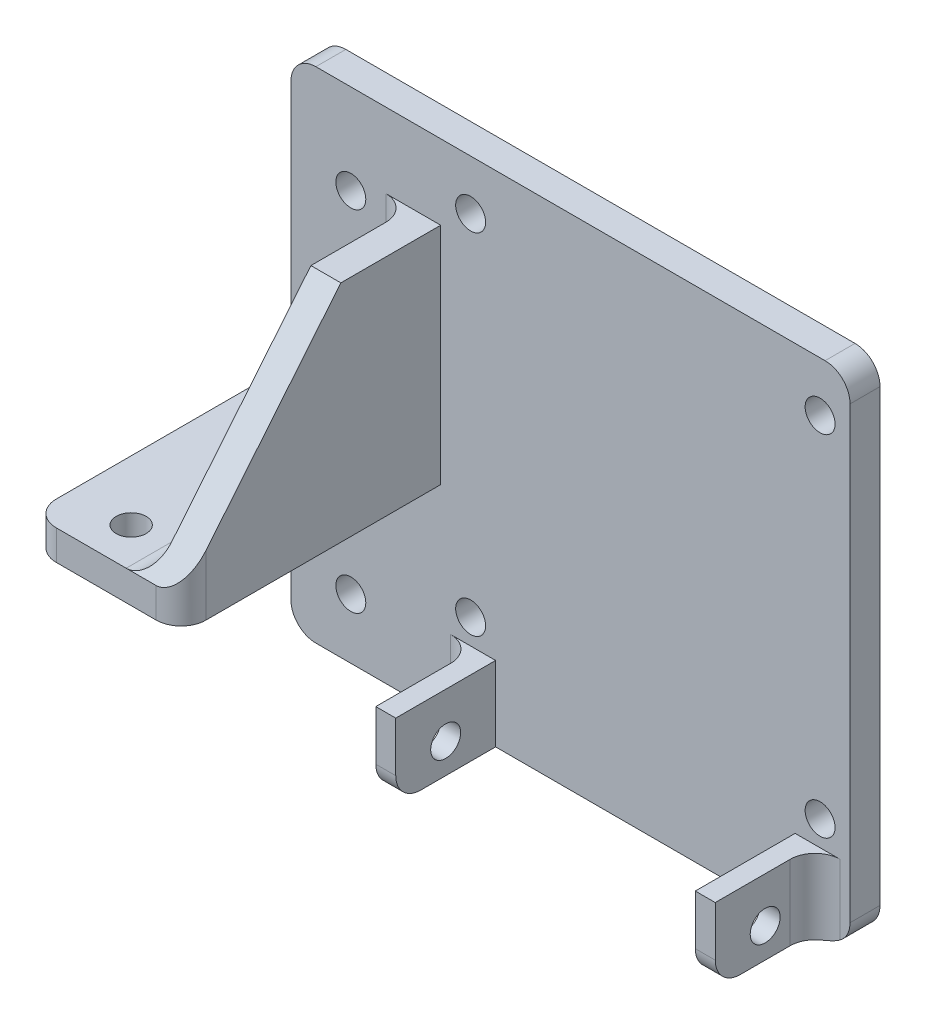
SolidWorks part; units mm, degrees
ref_plane "Front Plane" through (0, 0, 0) normal (0, 0, 1) x (1, 0, 0)
ref_plane "Top Plane" through (0, 0, 0) normal (0, 1, 0) x (1, 0, 0)
ref_plane "Right Plane" through (0, 0, 0) normal (1, 0, 0) x (0, 0, -1)
sketch "Sketch1" plane through (0, 0, 0) normal (0, 0, 1) x (1, 0, 0)
  line L1 (0, 0) -> (56, 0)
  line L2 (0, 0) -> (0, 50)
  line L3 (0, 50) -> (56, 50)
  line L4 (56, 0) -> (56, 50)
  dimension "D1" = 56
  dimension "D2" = 50
extrude "Boss-Extrude1" add sketch "Sketch1" along normal blind 3
sketch "Sketch2" plane through (0, 0, 3) normal (0, 0, 1) x (1, 0, 0)
  line L0 (6, -4.5714) -> (6, 59.5728) construction
  line L1 (18, 10) -> (53, 10) construction
  line L2 (18, 10) -> (18, 45) construction
  line L3 (18, 45) -> (53, 45) construction
  line L4 (53, 10) -> (53, 45) construction
  circle A3 centre (18, 10) radius 1.5
  circle A4 centre (18, 45) radius 1.5
  circle A5 centre (53, 45) radius 1.5
  circle A6 centre (53, 10) radius 1.5
  circle A7 centre (6, 6) radius 1.5
  circle A8 centre (6, 41) radius 1.5
  dimension "D1" = 3
  dimension "D8" = 3
  dimension "D2" = 35
  dimension "D3" = 35
  dimension "D4" = 12
  dimension "D5" = 10
  dimension "D6" = 35
  dimension "D7" = 6
  dimension "D9" = 6
extrude "Cut-Extrude1" cut sketch "Sketch2" against normal through all
sketch "Sketch3" plane through (0, 0, 3) normal (0, 0, 1) x (1, 0, 0)
  line L0 (0, 50) -> (0, 0) construction
  line L1 (0, 20) -> (12, 20)
  line L2 (0, 20) -> (0, 23)
  line L3 (0, 23) -> (12, 23)
  line L4 (12, 20) -> (12, 23)
  dimension "D1" = 3
  dimension "D2" = 12
  dimension "D3" = 20
extrude "Boss-Extrude2" add sketch "Sketch3" along normal blind 26
sketch "Sketch5" plane through (0, 23, 0) normal (0, 1, 0) x (1, 0, 0)
  line L0 (6, -29.5175) -> (6, 3.8156) construction
  line L1 (0, -29) -> (0, -3) construction
  line L5 (56, -3) -> (0, -3) construction
  circle A0 centre (6, -7) radius 1.5
  circle A1 centre (6, -25) radius 1.5
  dimension "D2" = 3
  dimension "D1" = 6
  dimension "D3" = 18
  dimension "D4" = 4
extrude "Cut-Extrude2" cut sketch "Sketch5" against normal blind 10
sketch "Sketch6" plane through (12, 0, 0) normal (1, 0, 0) x (0, 0, -1)
  line L0 (-3, 20) -> (-29, 20)
  line L1 (-29, 20) -> (-29, 23)
  line L3 (-3, 42.5) -> (-3, 20)
  line L5 (-3, 0) -> (-3, 50) construction
  line L6 (-3, 42.5) -> (-13, 42.5)
  line L7 (-13, 42.5) -> (-29, 23)
  line L8 (-3, 50) -> (0, 50) construction
  dimension "D1" = 7.5
  dimension "D2" = 10
extrude "Boss-Extrude3" add sketch "Sketch6" along normal blind 3
sketch "Sketch7" plane through (0, 0, 3) normal (0, 0, 1) x (1, 0, 0)
  line L0 (0, 0) -> (56, 0) construction
  line L1 (18.5, 0) -> (20.5, 0)
  line L2 (18.5, 0) -> (18.5, 7.5)
  line L4 (20.5, 0) -> (20.5, 7.5)
  line L6 (52.5, 0) -> (50.5, 0)
  line L7 (52.5, 0) -> (52.5, 7.5)
  line L13 (18.5, 7.5) -> (20.5, 7.5)
  line L14 (50.5, 7.5) -> (50.5, 0)
  line L15 (50.5, 7.5) -> (52.5, 7.5)
  dimension "D1" = 7.5
  dimension "D2" = 7.5
  dimension "D3" = 18.5
  dimension "D4" = 2
  dimension "D5" = 30
extrude "Boss-Extrude4" add sketch "Sketch7" along normal blind 10
sketch "Sketch8" plane through (18.5, 0, 0) normal (-1, 0, 0) x (0, 0, 1)
  line L0 (3, 3) -> (13, 3) construction
  line L3 (13, 0) -> (3, 0) construction
  line L6 (13, 7.5) -> (13, 0) construction
  circle A0 centre (8, 3) radius 1.5
  dimension "D1" = 3
  dimension "D2" = 3
  dimension "D3" = 5
extrude "Cut-Extrude3" cut sketch "Sketch8" against normal through all
fillet "Fillet1" radius 2.5 4 edges at (0, 50, 1.5) (0, 0, 1.5) (56, 0, 1.5) (56, 50, 1.5)
fillet "Fillet2" radius 2.5 5 edges at (18.5, 3.75, 3) (12, 23, 16) (12, 32.75, 3) (52.5, 3.75, 3) (6, 23, 3)
fillet "Fillet3" radius 2.5 2 edges at (0, 21.5, 29) (15, 21.5, 29)
fillet "Fillet4" radius 2.5 2 edges at (51.5, 0, 13) (19.5, 0, 13)
